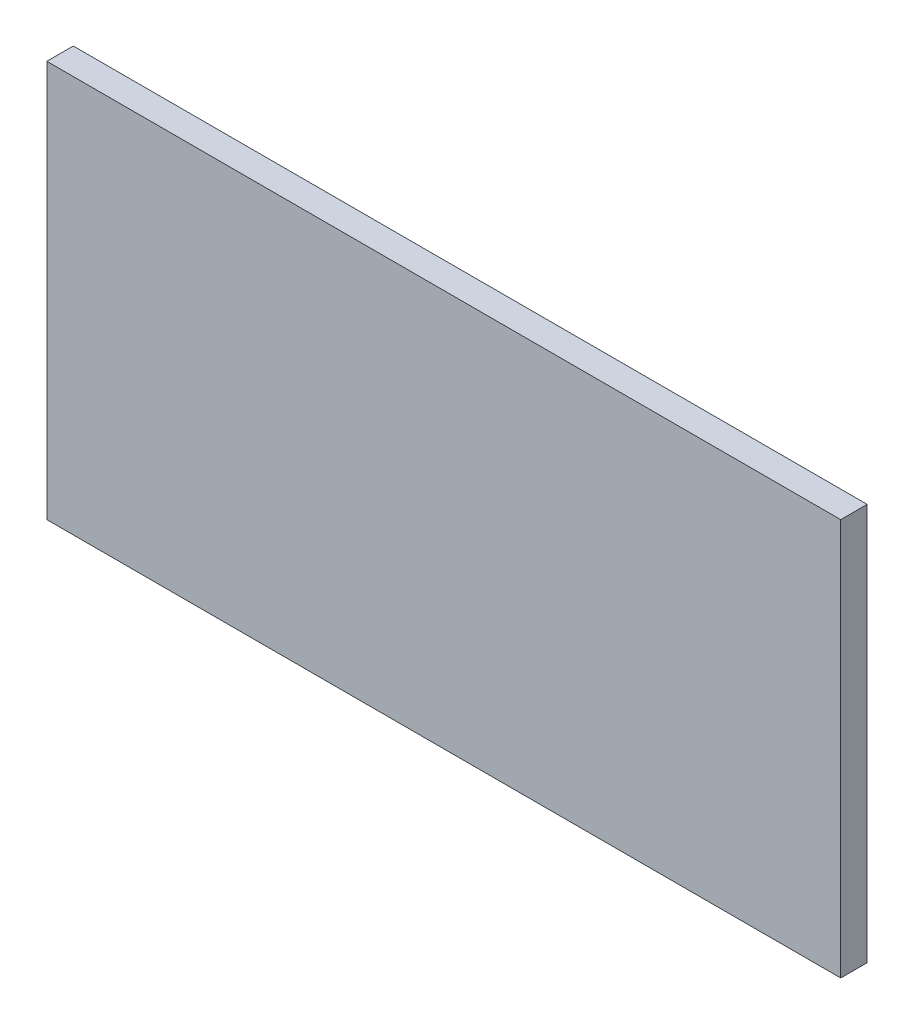
SolidWorks part; units mm, degrees
ref_plane "Front Plane" through (0, 0, 0) normal (0, 0, 1) x (1, 0, 0)
ref_plane "Top Plane" through (0, 0, 0) normal (0, 1, 0) x (1, 0, 0)
ref_plane "Right Plane" through (0, 0, 0) normal (1, 0, 0) x (0, 0, -1)
sketch "Sketch4" plane through (0, 0, 0) normal (0, 0, 1) x (1, 0, 0)
  line L1 (-762, 381) -> (762, 381)
  line L2 (-762, 381) -> (-762, -381)
  line L3 (-762, -381) -> (762, -381)
  line L4 (762, 381) -> (762, -381)
  line L5 (-762, 381) -> (762, -381) construction
  line L6 (-762, -381) -> (762, 381) construction
  point P0 (0, 0)
  dimension "D1" = 1524
  dimension "D2" = 762
extrude "Boss-Extrude1" add sketch "Sketch4" along normal blind 50.8
